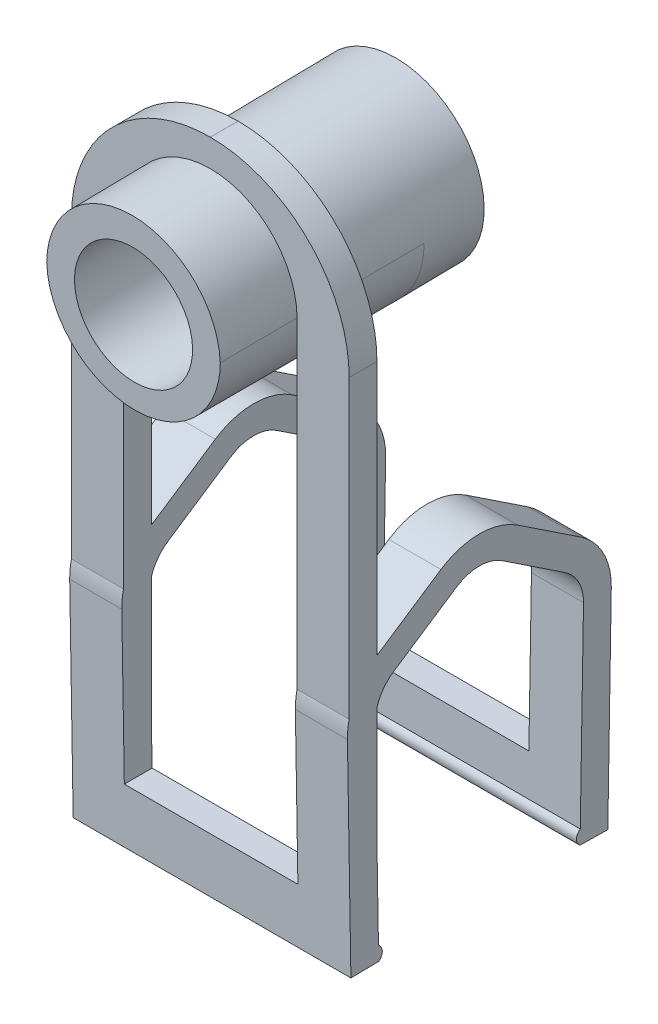
SolidWorks part; units mm, degrees
ref_plane "Front Plane" through (0, 0, 0) normal (0, 0, 1) x (1, 0, 0)
ref_plane "Top Plane" through (0, 0, 0) normal (0, 1, 0) x (1, 0, 0)
ref_plane "Right Plane" through (0, 0, 0) normal (1, 0, 0) x (0, 0, -1)
sketch "Sketch1" plane through (0, 0, 0) normal (1, 0, 0) x (0, 0, -1)
  line L0 (-7.25, -11.6388) -> (-7.5, 3.3591)
  line L1 (-6.1603, 5.908) -> (-1.6599, 8.8974)
  line L2 (1.6599, 8.8974) -> (6.1603, 5.908)
  line L3 (7.5, 3.3591) -> (7.25, -11.6388)
  line L4 (0, 0) -> (0, 10) construction
  line L5 (7.5274, 5) -> (-7.5274, 5) construction
  arc A0 (-7.5, 3.3591) -> (-6.1603, 5.908) centre (-4.5004, 3.4091) cw
  arc A1 (6.1603, 5.908) -> (7.5, 3.3591) centre (4.5004, 3.4091) cw
  arc A2 (-1.6599, 8.8974) -> (1.6599, 8.8974) centre (0, 6.3985) cw
  dimension "D4" = 3
  dimension "D1" = 15
  dimension "D2" = 10
  dimension "D3" = 5
  dimension "D5" = 15
  dimension "D6" = 15
  dimension "D7" = 14.5
extrude "Extrude-Thin1" add sketch "Sketch1" along normal mid plane 20 thin thin type one direction reverse wall 2
sketch "Sketch3" plane through (0, 0, 0) normal (1, 0, 0) x (0, 0, -1)
  line L0 (-9.3747, -4.1732) -> (-9.3747, 35.8268)
  line L1 (-9.2497, -11.6722) -> (-9.4997, 3.3258) construction
  dimension "D1" = 40
extrude "Extrude-Thin2" add sketch "Sketch3" along normal mid plane 20 thin thin type one direction wall 2
sketch "Sketch5" plane through (0, -0.1574, 9.4417) normal (0, -0.0167, 0.9999) x (1, 0, 0)
  line L0 (0, 27.7659) -> (0, 0) construction
  line L1 (0, 27.7659) -> (0, 35.9781) construction
  line L2 (10, 35.9781) -> (-10, 35.9781) construction
  line L3 (0, 35.9781) -> (8.2122, 35.9781) construction
  circle A0 centre (0, 27.7659) radius 4.25
  dimension "D1" = 8.5
extrude "Cut-Extrude1" cut sketch "Sketch5" against normal blind 3
extrude "Extrude-Thin3" add sketch "Sketch5<2>" along normal blind 5 and the other way blind 14 thin thin type one direction wall 2
sketch "Sketch5<2>" plane through (0, -0.1574, 9.4417) normal (0, -0.0167, 0.9999) x (1, 0, 0) same geometry as "Sketch5"
fillet "Fillet1" radius 9.99 2 edges at (-10, 35.8268, 8.3747) (10, 35.8268, 8.3747)
sketch "Sketch6" plane through (0, 0, 0) normal (0, 0, 1) x (1, 0, 0)
  line L0 (0, 0) -> (0, 27.7667) construction
  line L1 (6.25, -7.6722) -> (-6.25, -7.6722)
  line L2 (6.25, -7.6722) -> (6.25, 27.7667)
  line L3 (6.25, 27.7667) -> (-6.25, 27.7667)
  line L4 (-6.25, -7.6722) -> (-6.25, 27.7667)
  line L6 (10, -11.6722) -> (-10, -11.6722) construction
  circle A1 centre (0, 27.7659) radius 6.25
  dimension "D2" = 4
extrude "Cut-Extrude3" cut sketch "Sketch6" against normal through all both and the other way through all contours A1 L4 L1 L2 region at (0, 7.6244, 0)
sketch "Sketch7" plane through (10, 0, 0) normal (1, 0, 0) x (0, 0, -1)
  line L0 (-7.25, -11.6388) -> (-7.3747, -4.1565) construction
  line L1 (7.5, 3.3591) -> (7.25, -11.6388) construction
  line L2 (-7.2667, -10.6388) -> (-7.25, -11.6388)
  line L3 (7.2667, -10.6388) -> (7.25, -11.6388)
  arc A0 (-7.25, -11.6388) -> (-7.2667, -10.6388) centre (-7.5898, -11.1443) ccw
  arc A1 (7.25, -11.6388) -> (7.2667, -10.6388) centre (7.5898, -11.1443) cw
  dimension "D2" = 0.6
  dimension "D4" = 0.6
  dimension "D1" = 1
  dimension "D3" = 1
extrude "Boss-Extrude1" add sketch "Sketch7" against normal up to surface (20 mm away) up to face at (-10, 4.5232, 1.9076)
